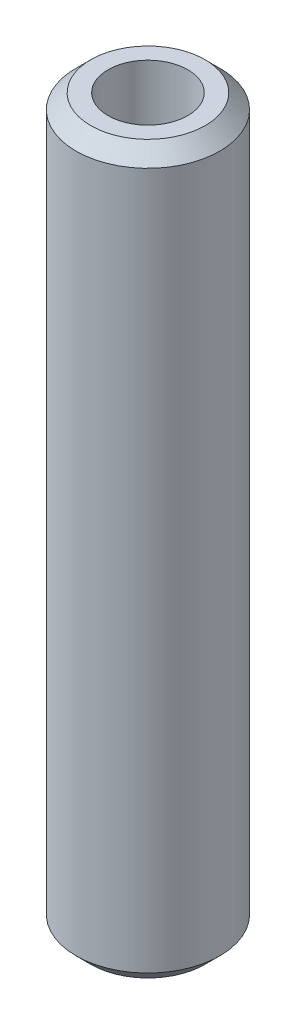
SolidWorks part; units mm, degrees
ref_plane "Front Plane" through (0, 0, 0) normal (0, 0, 1) x (1, 0, 0)
ref_plane "Top Plane" through (0, 0, 0) normal (0, 1, 0) x (1, 0, 0)
ref_plane "Right Plane" through (0, 0, 0) normal (1, 0, 0) x (0, 0, -1)
sketch "Sketch1" plane through (0, 0, 0) normal (0, 1, 0) x (1, 0, 0)
  circle A0 centre (0, 0) radius 17.5
  dimension "SHAFT_OD" = 35
extrude "Boss-Extrude1" add sketch "Sketch1" along normal blind 176.8377
sketch "Sketch2" plane through (0, 0, 0) normal (0, 1, 0) x (1, 0, 0)
  circle A0 centre (0, 0) radius 9.6977
  dimension "BORE_D" = 19.3954
extrude "Cut-Extrude1" cut sketch "Sketch2" along normal through all
chamfer "Chamfer1" distance 3.5804 angle 45 2 edges at (0, 176.8377, 17.5) (0, 0, 17.5)
